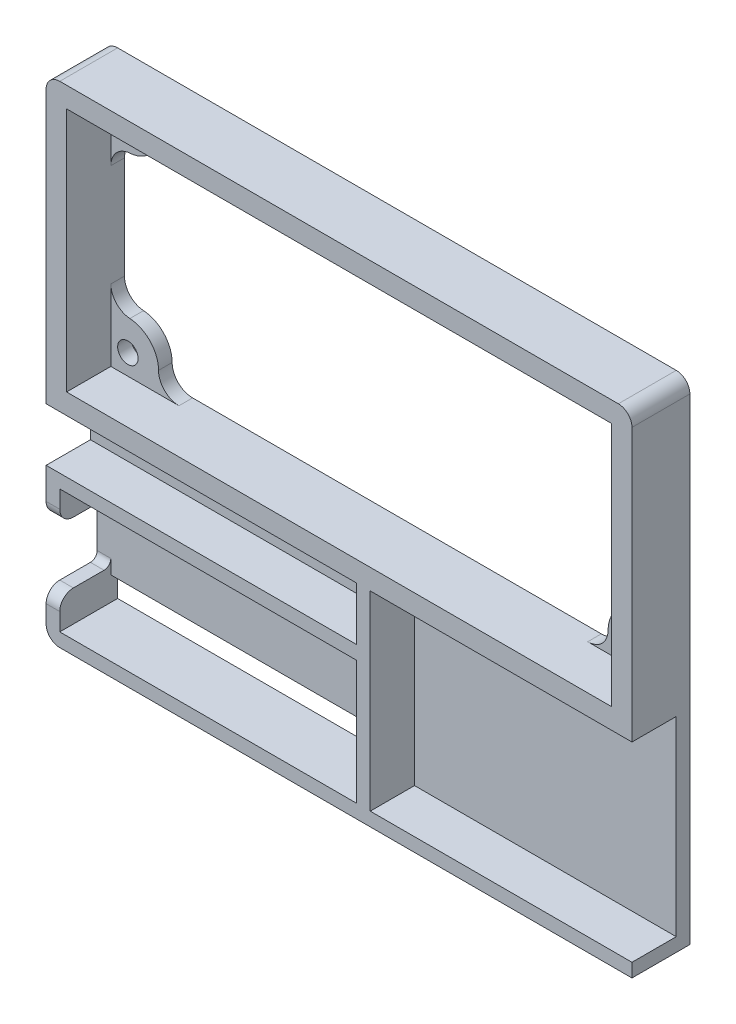
SolidWorks part; units mm, degrees
ref_plane "Front Plane" through (0, 0, 0) normal (0, 0, 1) x (1, 0, 0)
ref_plane "Top Plane" through (0, 0, 0) normal (0, 1, 0) x (1, 0, 0)
ref_plane "Right Plane" through (0, 0, 0) normal (1, 0, 0) x (0, 0, -1)
sketch "Sketch1" plane through (0, 0, 0) normal (0, 0, 1) x (1, 0, 0)
  line L0 (-2, -2) -> (-2, 4.59)
  line L1 (0, 0) -> (43.58, 0)
  line L2 (0, 0) -> (0, 4.59)
  line L3 (0, 18.18) -> (43.58, 18.18)
  line L4 (43.58, 0) -> (43.58, 18.18)
  line L5 (-2, 20.18) -> (45.58, 20.18)
  line L6 (45.58, -2) -> (45.58, 20.18)
  line L7 (-2, -2) -> (45.58, -2)
  line L9 (0, 13.59) -> (-2, 13.59)
  line L10 (0, 4.59) -> (-2, 4.59)
  line L11 (-2, 13.59) -> (-2, 20.18)
  line L12 (-2, -2) -> (-2, 20.18) construction
  line L13 (0, 13.59) -> (0, 18.18)
  line L14 (0, 0) -> (0, 18.18) construction
  point P12 (0, 9.09)
  dimension "D1" = 18.18
  dimension "D2" = 43.58
  dimension "D3" = 2
extrude "Boss-Extrude1" add sketch "Sketch1" along normal blind 7.5
sketch "Sketch2" plane through (0, 0, 0) normal (0, 0, -1) x (-1, 0, 0)
  line L1 (2, 20.18) -> (-45.58, 20.18)
  line L2 (2, 20.18) -> (2, -2)
  line L3 (2, -2) -> (-45.58, -2)
  line L4 (-45.58, 20.18) -> (-45.58, -2)
  line L5 (0, 18.18) -> (-43.58, 18.18)
  line L6 (0, 18.18) -> (0, 0)
  line L7 (0, 0) -> (-43.58, 0)
  line L8 (-43.58, 18.18) -> (-43.58, 0)
  line L9 (0, 18.18) -> (-43.58, 18.18)
  line L10 (0, 18.18) -> (0, 14.68)
  line L11 (0, 14.68) -> (-43.58, 14.68)
  line L12 (-43.58, 18.18) -> (-43.58, 14.68)
  line L13 (-43.58, 0) -> (0, 0)
  line L14 (-43.58, 0) -> (-43.58, 3.5)
  line L15 (-43.58, 3.5) -> (0, 3.5)
  line L16 (0, 0) -> (0, 3.5)
  line M1 (0, 4.59) -> (0, 0)
  line M2 (0, 0) -> (-43.58, 0)
  line M3 (-43.58, 0) -> (-43.58, 18.18)
  line M4 (-43.58, 18.18) -> (0, 18.18)
  line M5 (0, 18.18) -> (0, 13.59)
  line M6 (0, 13.59) -> (2, 13.59)
  line M7 (2, 13.59) -> (2, 20.18)
  line M8 (2, 20.18) -> (-45.58, 20.18)
  line M9 (-45.58, 20.18) -> (-45.58, -2)
  line M10 (-45.58, -2) -> (2, -2)
  line M11 (2, -2) -> (2, 4.59)
  line M12 (2, 4.59) -> (0, 4.59)
  dimension "D1" = 3.5
  dimension "D2" = 3.5
  dimension "D3" = 43.58
extrude "Boss-Extrude2" add sketch "Sketch2" along normal blind 1 contours L6 L2 M6 M12 | L8 L15 L6 L11 M1 | L6 L8 M12 M1 M2 M3 M4 M5 M6 M7 M8 M9 M10 M11 region at (-1.475, 16.885, 0) region at (-1, 9.09, 0) region at (21.79, 9.09, 0)
sketch "Sketch3" plane through (0, 0, -1) normal (0, 0, -1) x (-1, 0, 0)
  line L16 (0, 18.18) -> (2, 18.18)
  line L17 (2, 20.18) -> (2, 18.18)
  line L19 (-45.58, -2) -> (2, -2) construction
  line L21 (-45.58, -2) -> (-84, -2)
  line L22 (-45.58, -2) -> (-45.58, 0)
  line L23 (-45.58, 0) -> (-84, 0)
  line L24 (-84, -2) -> (-84, 0)
  line L25 (-84, 0) -> (-45.58, 0)
  line L26 (-84, 0) -> (-84, 28)
  line L27 (-84, 28) -> (-45.58, 28)
  line L28 (-45.58, 0) -> (-45.58, 28)
  line L29 (2, 20.18) -> (-45.58, 20.18)
  line L30 (2, 20.18) -> (2, 28)
  line L31 (2, 28) -> (-45.58, 28)
  line L32 (-45.58, 20.18) -> (-45.58, 28)
  point P9 (-41.6533, 49)
  point P12 (0, 0)
  point P13 (0, 0)
  line B0 (2, 70) -> (-84, 70)
  line B1 (-1, 31) -> (-81, 31)
  line B2 (-1, 31) -> (-1, 67)
  line B3 (-1, 67) -> (-81, 67)
  line B4 (-81, 31) -> (-81, 67)
  line B5 (-84, 28) -> (-84, 70)
  line B6 (2, 28) -> (-84, 28)
  line B7 (2, 28) -> (2, 70)
  circle B8 centre (-3.5, 64) radius 1.5
  circle B9 centre (-78.5, 64) radius 1.5
  circle B10 centre (-3.5, 34) radius 1.5
  circle B11 centre (-78.5, 34) radius 1.5
  arc B12 (-6.8541, 67) -> (-1, 60.2583) centre (-3.5, 64) ccw
  arc B13 (-1, 37.7417) -> (-6.8541, 31) centre (-3.5, 34) ccw
  arc B14 (-75.1459, 31) -> (-81, 37.7417) centre (-78.5, 34) ccw
  arc B15 (-81, 60.2583) -> (-75.1459, 67) centre (-78.5, 64) ccw
  line M27 (2, 20.18) -> (-45.58, 20.18)
  line M28 (-45.58, 20.18) -> (-45.58, -2)
  dimension "D1" = 30
  dimension "D2" = 2
sketch_block_instance "Block1-1"
sketch_block "Block1" parameters "D5"=3, "D6"=3, "D7"=3, "D8"=3, "D1"=36, "D2"=80, "D3"=30, "D4"=75
extrude "Boss-Extrude3" add sketch "Sketch3" against normal up to surface (8.5 mm away) contours B7 B0 B5 B6 B1 B4 B3 B2 M27 M28 | L24 L21 L23 M28 region at (64.79, -1, -1) region at (83.0429, 49, -1) up to face at (14.1933, 9.09, 7.5)
extrude "Boss-Extrude4" add sketch "Sketch3<3>" against normal blind 2 contours B2 B13 B1 B10 | B3 B12 B2 B8 | B4 B15 B3 B9 | B1 B14 B4 B11 | L30 L31 L28 M27 | L28 L27 L26 L23 M28 region at (64.79, 14, -1) region at (21.79, 24.09, -1) region at (3.9271, 31.1026, -1) region at (78.0729, 31.1026, -1) region at (6.8203, 61.1168, -1) region at (80.8974, 63.6292, -1)
sketch "Sketch3<3>" plane through (0, 0, -1) normal (0, 0, -1) x (-1, 0, 0) same geometry as "Sketch3"
fillet "Fillet1" radius 3 8 edges at (75.1459, 31, 0) (81, 37.7417, 0) (81, 60.2583, 0) (75.1459, 67, 0) (6.8541, 67, 0) (6.8541, 31, 0) (1, 37.7417, 0) (1, 60.2583, 0)
fillet "Fillet2" radius 2 3 edges at (-2, -2, 3.25) (84, 70, 3.25) (-2, 70, 3.25)
sketch "Sketch6" plane through (0, 0, 1) normal (0, 0, 1) x (1, 0, 0)
  line L0 (-2, 28) -> (84, 28) construction
  line L1 (45.58, 20.18) -> (43.58, 20.18)
  line L2 (45.58, 20.18) -> (45.58, 28)
  line L3 (45.58, 28) -> (43.58, 28)
  line L4 (43.58, 20.18) -> (43.58, 28)
  dimension "D1" = 2
extrude "Boss-Extrude5" add sketch "Sketch6" along normal up to surface (6.5 mm away) up to face at (22.5271, 7.2444, 7.5)
fillet "Fillet3" radius 1 2 edges at (-1, 4.59, 0) (-1, 13.59, 0)
fillet "Fillet4" radius 2 2 edges at (-1, 4.59, 7.5) (-1, 13.59, 7.5)
